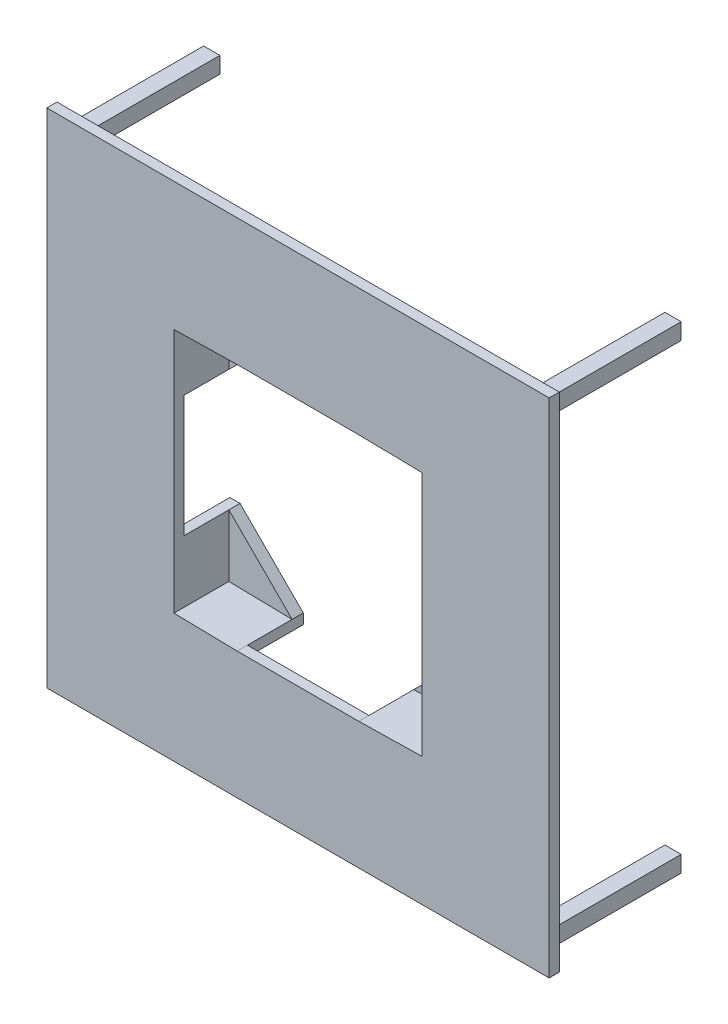
SolidWorks part; units mm, degrees
ref_plane "Plano frontal" through (0, 0, 0) normal (0, 0, 1) x (1, 0, 0)
ref_plane "Plano superior" through (0, 0, 0) normal (0, 1, 0) x (1, 0, 0)
ref_plane "Plano direito" through (0, 0, 0) normal (1, 0, 0) x (0, 0, -1)
sketch "Esboço1" plane through (0, 0, 0) normal (0, 0, 1) x (1, 0, 0)
  line L0 (-123.5, 123.5) -> (123.5, -123.5) construction
  line L1 (-123.5, 123.5) -> (123.5, 123.5)
  line L2 (-123.5, 123.5) -> (-123.5, -123.5)
  line L3 (-123.5, -123.5) -> (123.5, -123.5)
  line L4 (123.5, 123.5) -> (123.5, -123.5)
  line L5 (-123.5, -123.5) -> (123.5, 123.5) construction
  point P4 (0, 0)
  dimension "D1" = 247
  dimension "D2" = 247
extrude "Ressalto-extrusão1" add sketch "Esboço1" along normal blind 5
sketch "Esboço3" plane through (0, 0, 5) normal (0, 0, 1) x (1, 0, 0)
  line L0 (-123.5, 123.5) -> (123.5, -123.5) construction
  line L1 (-123.5, -123.5) -> (123.5, 123.5) construction
  line L2 (-61, 61) -> (61, -61) construction
  line L3 (-61, 61) -> (61, 61)
  line L4 (-61, 61) -> (-61, -61)
  line L5 (-61, -61) -> (61, -61)
  line L6 (61, 61) -> (61, -61)
  line L7 (-61, -61) -> (61, 61) construction
  point P12 (0, 0)
  point P15 (0, 0)
  dimension "D1" = 122
extrude "Corte-extrusão2" cut sketch "Esboço3" against normal through all
sketch "Esboço4" plane through (0, 0, 0) normal (0, 0, -1) x (-1, 0, 0)
  line L0 (-61, 29.9002) -> (-66, 29.9002)
  line L1 (-61, -61) -> (-61, 61) construction
  line L2 (-66, 29.9002) -> (-66, 66)
  line L3 (-66, 66) -> (-29.9002, 66)
  line L4 (-29.9002, 66) -> (-29.9002, 61)
  line L5 (-61, 61) -> (61, 61) construction
  line L6 (-29.9002, 61) -> (-61, 29.9002)
  line L7 (0, 0) -> (0, 123.5) construction
  line L8 (-123.5, 123.5) -> (123.5, 123.5) construction
  line L9 (0, 0) -> (0, -123.5) construction
  line L10 (123.5, -123.5) -> (-123.5, -123.5) construction
  line L11 (-123.5, 0) -> (123.5, 0) construction
  line L12 (-123.5, -123.5) -> (-123.5, 123.5) construction
  line L13 (123.5, 123.5) -> (123.5, -123.5) construction
  line L14 (29.9002, 61) -> (61, 29.9002)
  line L15 (29.9002, 66) -> (29.9002, 61)
  line L16 (66, 66) -> (29.9002, 66)
  line L17 (66, 29.9002) -> (66, 66)
  line L18 (61, 29.9002) -> (66, 29.9002)
  line L19 (61, -29.9002) -> (66, -29.9002)
  line L20 (66, -29.9002) -> (66, -66)
  line L21 (66, -66) -> (29.9002, -66)
  line L22 (29.9002, -66) -> (29.9002, -61)
  line L23 (29.9002, -61) -> (61, -29.9002)
  line L24 (-29.9002, -61) -> (-61, -29.9002)
  line L25 (-29.9002, -66) -> (-29.9002, -61)
  line L26 (-66, -66) -> (-29.9002, -66)
  line L27 (-66, -29.9002) -> (-66, -66)
  line L28 (-61, -29.9002) -> (-66, -29.9002)
  dimension "D1" = 5
  dimension "D2" = 5
extrude "Ressalto-extrusão2" add sketch "Esboço4" along normal blind 27.5 and the other way blind 5
sketch "Esboço5" plane through (0, 0, 5) normal (0, 0, 1) x (1, 0, 0)
  line L0 (-61, 29.9002) -> (-61, 60.395)
  line L1 (-29.9002, 61) -> (-61, 60.395)
  line L2 (-61, 29.9002) -> (-29.9002, 61)
  line L3 (0, 123.5) -> (0, -123.5) construction
  line L4 (123.5, 123.5) -> (-123.5, 123.5) construction
  line L5 (-123.5, -123.5) -> (123.5, -123.5) construction
  line L6 (-123.5, 0) -> (123.5, 0) construction
  line L7 (-123.5, 123.5) -> (-123.5, -123.5) construction
  line L8 (123.5, -123.5) -> (123.5, 123.5) construction
  line L9 (61, 29.9002) -> (29.9002, 61)
  line L10 (29.9002, 61) -> (61, 60.395)
  line L11 (61, 29.9002) -> (61, 60.395)
  line L12 (61, -29.9002) -> (61, -60.395)
  line L13 (29.9002, -61) -> (61, -60.395)
  line L14 (61, -29.9002) -> (29.9002, -61)
  line L15 (-61, -29.9002) -> (-29.9002, -61)
  line L16 (-29.9002, -61) -> (-61, -60.395)
  line L17 (-61, -29.9002) -> (-61, -60.395)
extrude "Corte-extrusão3" cut sketch "Esboço5" against normal blind 27
sketch "Esboço8" plane through (0, 0, 0) normal (0, 0, -1) x (-1, 0, 0)
  line L0 (0, 123.5) -> (0, -123.5) construction
  line L1 (109.4, -109.4) -> (117.4, -109.4)
  line L2 (109.4, -109.4) -> (109.4, -117.4)
  line L3 (109.4, -117.4) -> (117.4, -117.4)
  line L4 (117.4, -109.4) -> (117.4, -117.4)
  line L5 (-123.5, 123.5) -> (123.5, 123.5) construction
  line L6 (123.5, -123.5) -> (-123.5, -123.5) construction
  line L7 (-123.5, 0) -> (123.5, 0) construction
  line L8 (-123.5, -123.5) -> (-123.5, 123.5) construction
  line L9 (123.5, 123.5) -> (123.5, -123.5) construction
  line L22 (-117.4, -109.4) -> (-117.4, -117.4)
  line L23 (-109.4, -117.4) -> (-117.4, -117.4)
  line L24 (-109.4, -109.4) -> (-109.4, -117.4)
  line L25 (-109.4, -109.4) -> (-117.4, -109.4)
  line L26 (-109.4, 109.4) -> (-117.4, 109.4)
  line L27 (-109.4, 109.4) -> (-109.4, 117.4)
  line L28 (-109.4, 117.4) -> (-117.4, 117.4)
  line L29 (-117.4, 109.4) -> (-117.4, 117.4)
  line L30 (117.4, 109.4) -> (117.4, 117.4)
  line L31 (109.4, 117.4) -> (117.4, 117.4)
  line L32 (109.4, 109.4) -> (109.4, 117.4)
  line L33 (109.4, 109.4) -> (117.4, 109.4)
  dimension "D1" = 6.1
  dimension "D2" = 6.1
extrude "Ressalto-extrusão3" add sketch "Esboço8" along normal blind 66
